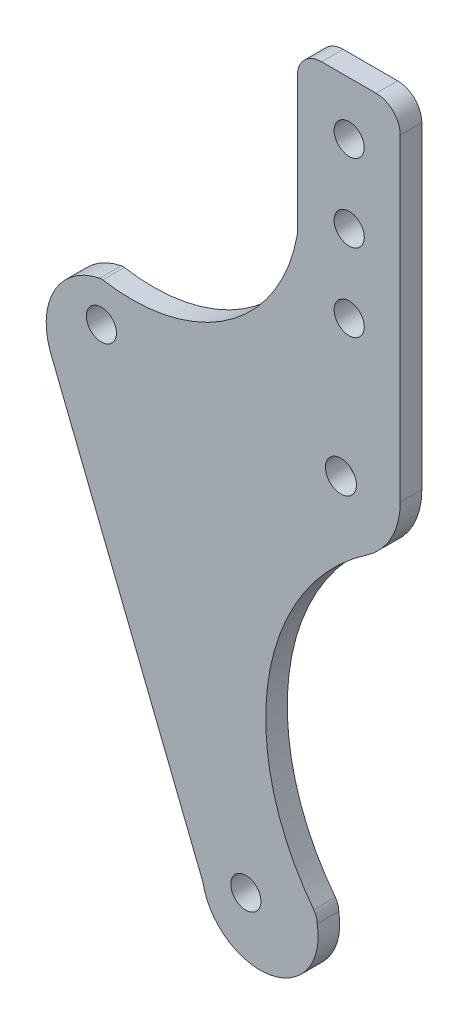
SolidWorks part; units mm, degrees
ref_plane "Front Plane" through (0, 0, 0) normal (0, 0, 1) x (1, 0, 0)
ref_plane "Top Plane" through (0, 0, 0) normal (0, 1, 0) x (1, 0, 0)
ref_plane "Right Plane" through (0, 0, 0) normal (1, 0, 0) x (0, 0, -1)
sketch "Sketch1" plane through (0, 0, 0) normal (0, 0, 1) x (1, 0, 0)
  line L0 (0, 0) -> (0, 30.156) construction
  line L1 (0, 0) -> (32.4691, 0) construction
  line L3 (-26.683, 26.3577) -> (-26.683, 6.3518)
  line L4 (-15.0841, 29.9137) -> (-23.127, 29.9137)
  line L5 (-63.1034, -26.9607) -> (-40.5959, -83.4559)
  line L7 (-11.5281, -20.4623) -> (-11.5281, 26.3577)
  line L8 (-40.5959, -83.4559) -> (-24.2809, -78.8021) construction
  circle A0 centre (-55.5441, -19.825) radius 2.2225
  circle A1 centre (-19.05, 22.085) radius 2.2225
  circle A2 centre (-19.05, -0.775) radius 2.2225
  arc A6 (-15.0841, 29.9137) -> (-11.5281, 26.3577) centre (-15.0841, 26.3577) cw
  arc A7 (-23.127, 29.9137) -> (-26.683, 26.3577) centre (-23.127, 26.3577) ccw
  arc A9 (-16.357, -29.5947) -> (-24.2809, -78.8021) centre (2.9569, -57.9465) ccw
  arc A11 (-16.357, -29.5947) -> (-11.5281, -20.4623) centre (-22.5782, -20.4623) ccw
  circle A14 centre (-34.2687, -81.6511) radius 2.2225
  arc A17 (-23.7579, -80.3848) -> (-24.2809, -78.8021) centre (-26.2976, -80.3463) ccw
  arc A21 (-40.5959, -83.4559) -> (-23.7579, -80.3848) centre (-32.1769, -81.9204) ccw
  arc A23 (-63.1034, -26.9607) -> (-55.7802, -14.0251) centre (-53.8578, -23.6541) cw
  circle A24 centre (-19.05, 10.655) radius 2.2225
  arc A25 (-55.3282, -14.0195) -> (-26.7251, 5.891) centre (-51.0844, 10.3846) ccw
  arc A26 (-55.3282, -14.0195) -> (-55.7802, -14.0251) centre (-55.5392, -15.2326) ccw
  arc A27 (-26.683, 6.3518) -> (-26.7251, 5.891) centre (-29.223, 6.3518) cw
  point P14 (-19.1056, 29.9137)
  point P24 (-15.2948, 26.5068)
  point P35 (-55.5441, -13.981)
  point P41 (-55.5441, -13.981)
  dimension "D1" = 4.445
  dimension "D2" = 2.54
  dimension "D3" = 3.556
  dimension "D4" = 34.3053
  dimension "D5" = 11.0501
  dimension "D6" = 8.5579
  dimension "D7" = 9.8191
  dimension "D11" = 11.5281
  dimension "D12" = 15.2948
  dimension "D13" = 19.05
  dimension "D10" = 2.9569
  dimension "D14" = 19.1056
  dimension "D15" = 24.2809
  dimension "D18" = 53.8578
  dimension "D19" = 55.3282
  dimension "D21" = 26.5068
  dimension "D22" = 29.9137
  dimension "D23" = 32.1769
  dimension "D24" = 34.2687
  dimension "D8" = 24.7703
  dimension "D9" = 1.2313
  dimension "D16" = 26.7251
  dimension "D17" = 23.7579
  dimension "D20" = 5.891
  dimension "D25" = 40.5959
  dimension "D26" = 10.655
  dimension "D27" = 22.085
  dimension "D28" = 20.4623
  dimension "D30" = 0.775
  dimension "D32" = 63.1034
  dimension "D36" = 19.825
extrude "Boss-Extrude1" add sketch "Sketch1" along normal blind 3.175
sketch "Sketch2" plane through (0, 0, 3.175) normal (0, 0, 1) x (1, 0, 0)
  line L0 (-11.5281, -20.4623) -> (-11.5281, 26.3577) construction
  line L1 (-15.0841, 29.9137) -> (-23.127, 29.9137) construction
  circle A0 centre (-20.2675, -21.5169) radius 2.286
  point P2 (-20.2675, -21.5169)
  dimension "D1" = 4.572
  dimension "D2" = 8.7394
  dimension "D3" = 51.4306
extrude "Cut-Extrude1" cut sketch "Sketch2" against normal through all
